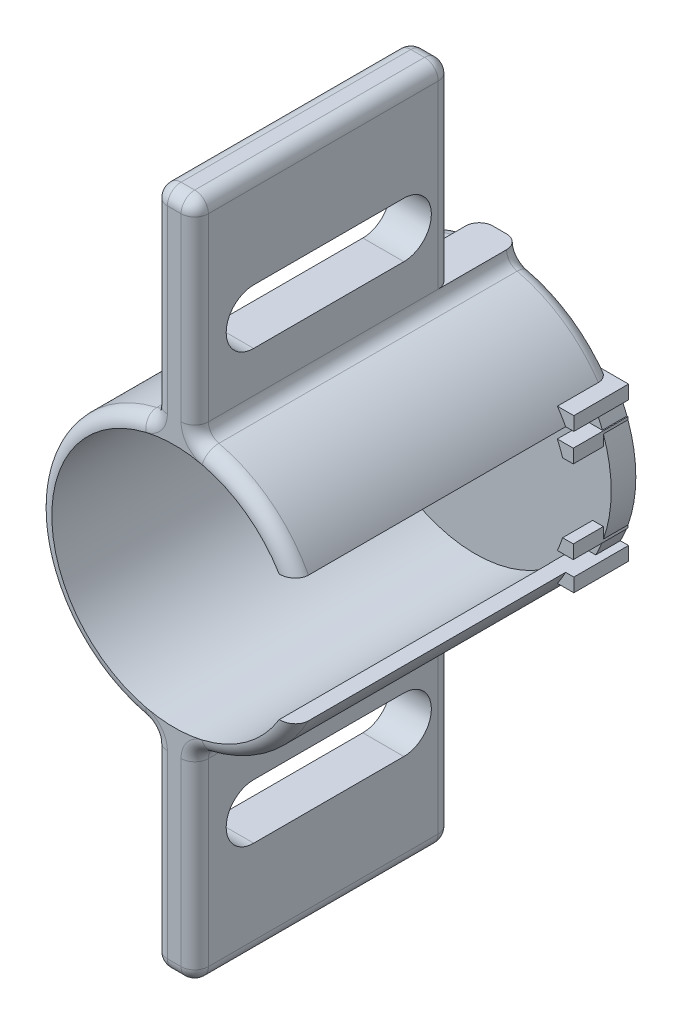
SolidWorks part; units mm, degrees
ref_plane "Front Plane" through (0, 0, 0) normal (0, 0, 1) x (1, 0, 0)
ref_plane "Top Plane" through (0, 0, 0) normal (0, 1, 0) x (1, 0, 0)
ref_plane "Right Plane" through (0, 0, 0) normal (1, 0, 0) x (0, 0, -1)
sketch "Sketch1" plane through (0, 0, 0) normal (0, 0, 1) x (1, 0, 0)
  line L0 (10.4361, 7.1253) -> (11.9601, 7.1253)
  line L1 (11.9601, 7.1253) -> (11.9601, 5.8553)
  line L2 (11.9601, 5.8553) -> (11.1981, 5.8553)
  line L3 (11.8143, 4.4837) -> (11.9083, 4.4837)
  line L4 (11.9083, 4.4837) -> (11.9083, 4.2277)
  line L5 (12.6365, 0) -> (-12.6365, 0) construction
  line L6 (11.9083, -4.4837) -> (11.9083, -4.2277)
  line L7 (11.8143, -4.4837) -> (11.9083, -4.4837)
  line L8 (11.9601, -5.8553) -> (11.1981, -5.8553)
  line L9 (11.9601, -7.1253) -> (11.9601, -5.8553)
  line L10 (10.4361, -7.1253) -> (11.9601, -7.1253)
  arc A0 (10.4361, 7.1253) -> (7.7334, 9.9937) centre (0, 0) ccw
  arc A1 (11.8143, 4.4837) -> (11.1981, 5.8553) centre (0, 0) ccw
  arc A2 (11.9083, -4.2277) -> (11.9083, 4.2277) centre (0, 0) ccw
  arc A3 (11.1981, -5.8553) -> (11.8143, -4.4837) centre (0, 0) ccw
  arc A4 (-6.1995, 11.0113) -> (-6.985, -10.5305) centre (0, 0) ccw
  arc A5 (7.1909, -10.3909) -> (10.4361, -7.1253) centre (0, 0) ccw
  arc A6 (-6.985, -10.5305) -> (7.1909, -10.3909) centre (0, 0) ccw
  arc A7 (-6.1995, 11.0113) -> (7.7334, 9.9937) centre (0, 0) cw
  dimension "D1" = 25.273
  dimension "D2" = 1.524
  dimension "D3" = 1.27
  dimension "D4" = 0.762
  dimension "D5" = 0.094
  dimension "D6" = 1.3716
  dimension "D7" = 13.97
extrude "Boss-Extrude1" add sketch "Sketch1" along normal blind 2.286
sketch "Sketch2" plane through (0, 0, 2.286) normal (0, 0, 1) x (1, 0, 0)
  line L0 (8.7851, 7.1253) -> (11.9601, 7.1253)
  line L1 (11.9601, 7.1253) -> (11.9601, 5.8553)
  line L2 (11.9601, 5.8553) -> (9.7274, 5.8553)
  line L3 (10.4249, 4.4837) -> (11.9083, 4.4837)
  line L4 (11.9083, 4.4837) -> (11.9083, 3.2137)
  line L5 (11.9083, 3.2137) -> (10.9177, 3.2137)
  line L6 (12.6365, 0) -> (-12.6365, 0) construction
  line L13 (11.9083, -3.2137) -> (10.9177, -3.2137)
  line L14 (11.9083, -4.4837) -> (11.9083, -3.2137)
  line L15 (10.4249, -4.4837) -> (11.9083, -4.4837)
  line L16 (11.9601, -5.8553) -> (9.7274, -5.8553)
  line L17 (11.9601, -7.1253) -> (11.9601, -5.8553)
  line L18 (8.7851, -7.1253) -> (11.9601, -7.1253)
  arc A0 (9.7274, 5.8553) -> (8.7851, 7.1253) centre (-0.8719, -1.0248) ccw
  arc A1 (10.9177, 3.2137) -> (10.4249, 4.4837) centre (-1.0924, -0.7157) ccw
  arc A6 (11.9083, -4.2277) -> (11.9083, 4.2277) centre (0, 0) ccw construction
  arc A7 (10.4361, 7.1253) -> (10.4361, -7.1253) centre (0, 0) ccw construction
  arc A8 (10.9177, -3.2137) -> (10.4249, -4.4837) centre (-1.0924, 0.7157) cw
  arc A9 (9.7274, -5.8553) -> (8.7851, -7.1253) centre (-0.8719, 1.0248) cw
  dimension "D6" = 12.6365
  dimension "D1" = 3.175
  dimension "D2" = 2.2327
  dimension "D3" = 1.4834
  dimension "D4" = 0.9906
  dimension "D5" = 1.27
extrude "Boss-Extrude2" add sketch "Sketch2" along normal blind 2.794
sketch "Sketch3" plane through (0, 0, 2.286) normal (0, 0, 1) x (1, 0, 0)
  line L1 (11.1981, 5.8553) -> (9.7423, 5.8553)
  line L2 (11.1981, -5.8553) -> (9.7274, -5.8553) construction
  line L3 (11.1981, -5.8553) -> (9.7423, -5.8553)
  line L6 (9.7274, 5.8553) -> (11.1981, 5.8553) construction
  arc A0 (11.1981, 5.8553) -> (11.1981, -5.8553) centre (0, 0) ccw
  arc A1 (10.4361, 7.1253) -> (10.4361, -7.1253) centre (0, 0) ccw construction
  arc A2 (9.7423, 5.8553) -> (9.7423, -5.8553) centre (0, 0) ccw
  arc A3 (10.0727, 5.2668) -> (10.0727, -5.2668) centre (0, 0) ccw construction
  dimension "D2" = 1.27
extrude "Boss-Extrude3" add sketch "Sketch3" along normal blind 27.94
ref_plane "Plane1" through (0, 0, 15.113) normal (0, 0, 1) x (1, 0, 0)
sketch "Sketch4" plane through (0, 0, 15.113) normal (0, 0, 1) x (1, 0, 0)
  line L0 (-1.905, -12.4921) -> (-1.905, -31.5421)
  line L1 (-1.905, -31.5421) -> (1.905, -31.5421)
  line L2 (1.905, -31.5421) -> (1.905, -12.4921)
  line L3 (-22.6399, 0) -> (22.0421, 0) construction
  line L4 (1.905, 31.5421) -> (1.905, 12.4921)
  line L5 (-1.905, 31.5421) -> (1.905, 31.5421)
  line L6 (-1.905, 12.4921) -> (-1.905, 31.5421)
  arc A0 (11.1981, 5.8553) -> (11.1981, -5.8553) centre (0, 0) ccw construction
  arc A1 (-1.905, -12.4921) -> (1.905, -12.4921) centre (0, 0) ccw
  arc A2 (-1.905, 12.4921) -> (1.905, 12.4921) centre (0, 0) cw
  point P5 (0, -31.5421)
  dimension "D1" = 3.81
  dimension "D2" = 19.05
extrude "Boss-Extrude4" add sketch "Sketch4" along normal mid plane 30.226
fillet "Fillet1" radius 1.27 25 edges at (7.344, -10.2833, 30.226) (7.344, 10.2833, 30.226) (-12.6365, 0, 30.226) (-12.6365, 0, 0) (6.7288, 10.696, 0) (6.7288, -10.696, 0) (1.905, -22.0171, 30.226) (-1.905, -22.0171, 30.226) (-1.905, -31.5421, 15.113) (0, -31.5421, 30.226) (-1.905, -22.0171, 0) (1.905, -22.0171, 0) (1.905, -31.5421, 15.113) (-1.905, -12.4921, 15.113) (1.905, -12.4921, 15.113) (-1.905, 22.0171, 30.226) (-1.905, 22.0171, 0) (1.905, 12.4921, 15.113) (1.905, 22.0171, 30.226) (1.905, 31.5421, 15.113) (1.905, 22.0171, 0) (0, 31.5421, 0) (0, 31.5421, 30.226) (-1.905, 31.5421, 15.113) (-1.905, 12.4921, 15.113)
hole_wizard "#10 Clearance Slot1" positions "Sketch7" profile "Sketch8" size "#10" standard "ANSI Inch" slot yes end condition through all
sketch "Sketch7" plane through (1.905, 0, 0) normal (1, 0, 0) x (0, 0, -1)
  line L0 (0, -13.5392) -> (0, -31.5421) construction
  line L1 (0, -31.5421) -> (-28.956, -31.5421) construction
  line L2 (-28.956, 31.5421) -> (-1.27, 31.5421) construction
  line L3 (0, 30.2721) -> (0, 13.5392) construction
  line L4 (-8.255, 19.8948) -> (-27.305, 19.8948) construction
  point P35 (-17.78, 19.8948)
  point P37 (-17.78, -19.8948)
  dimension "D1" = 17.78
  dimension "D2" = 11.6473
  dimension "D3" = 11.6473
  dimension "D4" = 17.78
  dimension "D5" = 19.05
sketch "Sketch8" plane through (1.905, 19.8948, 17.78) normal (0, 1, 0) x (0, 0, -1)
  line L0 (0, 0) -> (0, 14.5415)
  line L1 (0, 14.5415) -> (2.5527, 14.5415)
  line L2 (2.5527, 14.5415) -> (2.5527, 0)
  line L5 (2.5527, 0) -> (0, 0)
  line L11 (0, -6.35) -> (0, 107.95) construction
  dimension "Thru Hole Dia." = 5.1054
  dimension "Thru Hole Depth" = 14.5415
sketch "Sketch9" plane through (1.905, 0, 0) normal (1, 0, 0) x (0, 0, -1)
  line L0 (-1.27, -13.5392) -> (-28.956, -13.5392) construction
  line L1 (-6.35, -13.5392) -> (0, -13.5392)
  line L2 (-6.35, -13.5392) -> (-6.35, -31.5421)
  line L3 (-6.35, -31.5421) -> (0, -31.5421)
  line L4 (0, -13.5392) -> (0, -31.5421)
  line L5 (0, -31.5421) -> (-28.956, -31.5421) construction
  line L6 (0, -31.5421) -> (-1.27, -30.2721) construction
  line L7 (-28.956, 13.5392) -> (-1.27, 13.5392) construction
  line L8 (-6.35, 13.5392) -> (0, 13.5392)
  line L9 (-6.35, 13.5392) -> (-6.35, 31.5421)
  line L10 (-6.35, 31.5421) -> (0, 31.5421)
  line L11 (0, 13.5392) -> (0, 31.5421)
  dimension "D1" = 6.35
extrude "Cut-Extrude1" cut sketch "Sketch9" against normal through all
fillet "Fillet2" radius 1.27 10 edges at (-1.905, -21.9056, 6.35) (-1.533, -31.1701, 6.35) (0, -31.5421, 6.35) (1.533, -31.1701, 6.35) (-1.905, 21.9056, 6.35) (-1.533, 31.1701, 6.35) (0, 31.5421, 6.35) (1.533, 31.1701, 6.35) (1.905, -21.9056, 6.35) (1.905, 21.9056, 6.35)
